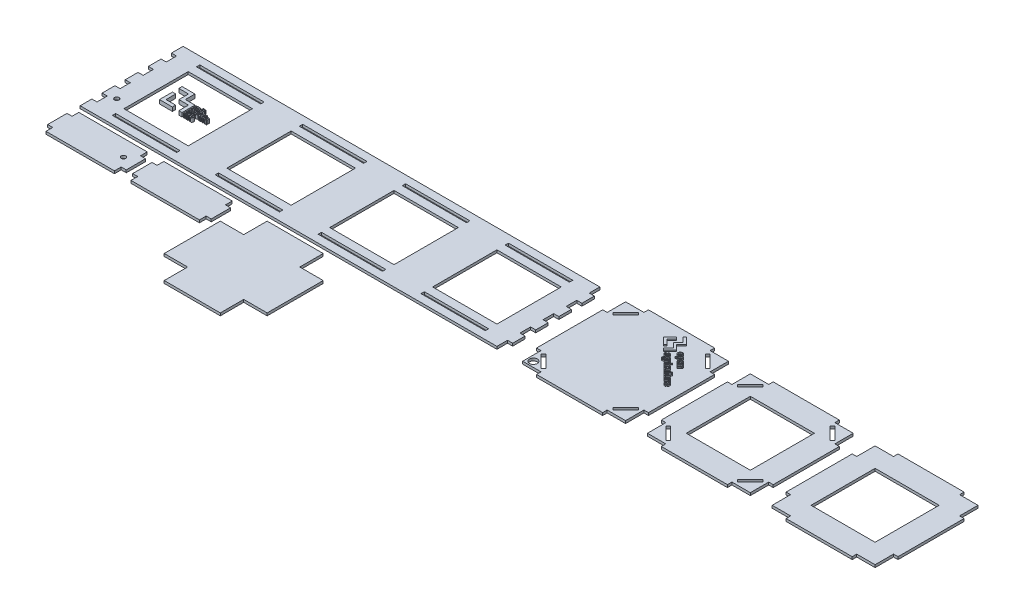
SolidWorks part; units mm, degrees
ref_plane "Front" through (0, 0, 0) normal (0, 0, 1) x (1, 0, 0)
ref_plane "Top" through (0, 0, 0) normal (0, 1, 0) x (1, 0, 0)
ref_plane "Right" through (0, 0, 0) normal (1, 0, 0) x (0, 0, -1)
sketch "Sketch1" plane through (0, 0, 0) normal (0, 1, 0) x (1, 0, 0)
  line L0 (0, 0) -> (152.4, 0) construction
  line L2 (-50.8, 50.8) -> (-50.8, -50.8) construction
  line L4 (50.8, 50.8) -> (50.8, -50.8) construction
  line L5 (-50.8, 50.8) -> (50.8, -50.8) construction
  line L6 (-50.8, -50.8) -> (50.8, 50.8) construction
  line L11 (50.8, 50.8) -> (152.4, 50.8)
  line L12 (50.8, 50.8) -> (50.8, -50.8) construction
  line L13 (50.8, -50.8) -> (152.4, -50.8)
  line L14 (152.4, 50.8) -> (152.4, -50.8) construction
  line L19 (-50.8, -50.8) -> (-152.4, -50.8)
  line L20 (-50.8, -50.8) -> (-50.8, 50.8) construction
  line L21 (-50.8, 50.8) -> (-152.4, 50.8)
  line L28 (50.8, -50.8) -> (-50.8, -50.8)
  line L34 (50.8, 50.8) -> (-50.8, 50.8)
  line L35 (-152.4, 50.8) -> (-152.4, -50.8) construction
  line L43 (-152.4, 50.8) -> (-254, 50.8)
  line L44 (-254, 50.8) -> (-254, -50.8) construction
  line L45 (-254, -50.8) -> (-152.4, -50.8)
  line L46 (152.4, 50.8) -> (152.4, 40.3352)
  line L47 (152.4, 40.3352) -> (157.48, 40.3352)
  line L48 (157.48, 40.3352) -> (157.48, 28.0162)
  line L49 (157.48, 28.0162) -> (152.4, 28.0162)
  line L50 (152.4, 28.0162) -> (152.4, 17.5514)
  line L51 (152.4, 17.5514) -> (157.48, 17.5514)
  line L63 (157.48, 17.5514) -> (157.48, 5.2324)
  line L64 (157.48, 5.2324) -> (152.4, 5.2324)
  line L65 (152.4, 5.2324) -> (152.4, -5.2324)
  line L66 (152.4, -5.2324) -> (157.48, -5.2324)
  line L67 (157.48, -5.2324) -> (157.48, -17.5514)
  line L68 (157.48, -17.5514) -> (152.4, -17.5514)
  line L69 (152.4, -17.5514) -> (152.4, -28.0162)
  line L70 (152.4, -28.0162) -> (157.48, -28.0162)
  line L71 (157.48, -28.0162) -> (157.48, -40.3352)
  line L72 (157.48, -40.3352) -> (152.4, -40.3352)
  line L73 (152.4, -40.3352) -> (152.4, -50.8)
  line L74 (-254, 50.8) -> (-259.08, 50.8)
  line L76 (-259.08, 39.2557) -> (-254, 39.2557)
  line L78 (-254, 29.0957) -> (-259.08, 29.0957)
  line L80 (-259.08, 16.4719) -> (-254, 16.4719)
  line L82 (-254, 6.3119) -> (-259.08, 6.3119)
  line L84 (-259.08, -6.3119) -> (-254, -6.3119)
  line L86 (-254, -16.4719) -> (-259.08, -16.4719)
  line L88 (-259.08, -29.0957) -> (-254, -29.0957)
  line L90 (-254, -39.2557) -> (-259.08, -39.2557)
  line L92 (-259.08, -50.8) -> (-254, -50.8)
  line L93 (157.48, 11.3919) -> (-254, 11.3919) construction
  line L94 (-254, 34.1757) -> (157.48, 34.1757) construction
  line L95 (-259.08, 50.8) -> (-259.08, 39.2557)
  line L96 (-259.08, 29.0957) -> (-259.08, 16.4719)
  line L97 (-254, 39.2557) -> (-254, 29.0957)
  line L98 (-254, 16.4719) -> (-254, 6.3119)
  line L99 (-254, -6.3119) -> (-254, -16.4719)
  line L100 (-254, -29.0957) -> (-254, -39.2557)
  line L101 (-254, -34.1757) -> (157.48, -34.1757) construction
  line L102 (-254, -11.3919) -> (157.48, -11.3919) construction
  line L103 (-259.08, 6.3119) -> (-259.08, -6.3119)
  line L104 (-259.08, -16.4719) -> (-259.08, -29.0957)
  line L105 (-259.08, -39.2557) -> (-259.08, -50.8)
  point P0 (0, 0)
  dimension "D1" = 101.6
  dimension "D2" = 101.6
  dimension "D3" = 5.08
  dimension "D4" = 12.319
  dimension "D5" = 10.16
extrude "Boss-Extrude1" add sketch "Sketch1" along normal blind 2.54
sketch "Sketch4" plane through (0, 2.54, 0) normal (0, 1, 0) x (1, 0, 0)
  line L0 (-152.4, 50.8) -> (-152.4, -50.8) construction
  line L1 (-152.4, 50.8) -> (-152.4, -50.8)
  line L2 (-50.8, 50.8) -> (-50.8, -50.8) construction
  line L3 (-50.8, 50.8) -> (-50.8, -50.8)
  line L4 (50.8, 50.8) -> (50.8, -50.8) construction
  line L5 (50.8, 50.8) -> (50.8, -50.8)
sketch "Sketch5" plane through (0, 2.54, 0) normal (0, 1, 0) x (1, 0, 0)
  line L0 (-254, -6.3119) -> (-254, 6.3119) construction
  line L1 (-152.4, 0) -> (-254, 0) construction
  line L2 (-152.4, 50.8) -> (-152.4, -50.8) construction
  line L3 (-152.4, 0) -> (-50.8, 0) construction
  line L4 (-50.8, 50.8) -> (-50.8, -50.8) construction
  line L5 (-50.8, 0) -> (50.8, 0) construction
  line L6 (50.8, 50.8) -> (50.8, -50.8) construction
  line L7 (50.8, 0) -> (152.4, 0) construction
  line L8 (152.4, -5.2324) -> (152.4, 5.2324) construction
  line L9 (-203.2, 0) -> (-203.2, -50.8) construction
  line L10 (-259.08, -50.8) -> (152.4, -50.8) construction
  line L11 (-101.6, 0) -> (-101.6, -50.8) construction
  line L12 (0, 0) -> (0, -50.8) construction
  line L13 (101.6, 0) -> (101.6, -50.8) construction
  line L14 (-171.45, -43.18) -> (-171.45, -50.8) construction
  line L15 (-234.95, -39.878) -> (-171.45, -39.878)
  line L16 (-234.95, -39.878) -> (-234.95, -43.18)
  line L17 (-234.95, -43.18) -> (-171.45, -43.18)
  line L18 (-171.45, -39.878) -> (-171.45, -43.18)
  line L19 (-234.95, -39.878) -> (-171.45, -43.18) construction
  line L20 (-234.95, -43.18) -> (-171.45, -39.878) construction
  line L21 (-133.35, -39.878) -> (-69.85, -39.878)
  line L22 (-133.35, -39.878) -> (-133.35, -43.18)
  line L23 (-133.35, -43.18) -> (-69.85, -43.18)
  line L24 (-69.85, -39.878) -> (-69.85, -43.18)
  line L25 (-133.35, -39.878) -> (-69.85, -43.18) construction
  line L26 (-133.35, -43.18) -> (-69.85, -39.878) construction
  line L27 (-31.75, -43.18) -> (31.75, -43.18)
  line L28 (-31.75, -43.18) -> (-31.75, -39.878)
  line L29 (-31.75, -39.878) -> (31.75, -39.878)
  line L30 (31.75, -43.18) -> (31.75, -39.878)
  line L31 (-31.75, -43.18) -> (31.75, -39.878) construction
  line L32 (-31.75, -39.878) -> (31.75, -43.18) construction
  line L33 (69.85, -43.18) -> (133.35, -43.18)
  line L34 (69.85, -43.18) -> (69.85, -39.878)
  line L35 (69.85, -39.878) -> (133.35, -39.878)
  line L36 (133.35, -43.18) -> (133.35, -39.878)
  line L37 (69.85, -43.18) -> (133.35, -39.878) construction
  line L38 (69.85, -39.878) -> (133.35, -43.18) construction
  line L39 (69.85, 39.878) -> (133.35, 43.18) construction
  line L40 (69.85, 43.18) -> (133.35, 39.878) construction
  line L41 (-31.75, 39.878) -> (31.75, 43.18) construction
  line L42 (-31.75, 43.18) -> (31.75, 39.878) construction
  line L43 (-133.35, 43.18) -> (-69.85, 39.878) construction
  line L44 (-133.35, 39.878) -> (-69.85, 43.18) construction
  line L45 (-234.95, 43.18) -> (-171.45, 39.878) construction
  line L46 (-234.95, 39.878) -> (-171.45, 43.18) construction
  line L47 (-171.45, 43.18) -> (-171.45, 50.8) construction
  line L48 (133.35, 43.18) -> (133.35, 39.878)
  line L49 (69.85, 39.878) -> (133.35, 39.878)
  line L50 (69.85, 43.18) -> (69.85, 39.878)
  line L51 (69.85, 43.18) -> (133.35, 43.18)
  line L52 (31.75, 43.18) -> (31.75, 39.878)
  line L53 (-31.75, 39.878) -> (31.75, 39.878)
  line L54 (-31.75, 43.18) -> (-31.75, 39.878)
  line L55 (-31.75, 43.18) -> (31.75, 43.18)
  line L56 (-69.85, 39.878) -> (-69.85, 43.18)
  line L57 (-133.35, 43.18) -> (-69.85, 43.18)
  line L58 (-133.35, 39.878) -> (-133.35, 43.18)
  line L59 (-133.35, 39.878) -> (-69.85, 39.878)
  line L60 (-171.45, 39.878) -> (-171.45, 43.18)
  line L61 (-234.95, 43.18) -> (-171.45, 43.18)
  line L62 (-234.95, 39.878) -> (-234.95, 43.18)
  line L63 (-234.95, 39.878) -> (-171.45, 39.878)
  line L65 (-234.95, 31.75) -> (-171.45, 31.75)
  line L66 (-234.95, 31.75) -> (-234.95, -31.75)
  line L67 (-234.95, -31.75) -> (-171.45, -31.75)
  line L68 (-171.45, 31.75) -> (-171.45, -31.75)
  line L69 (-234.95, 31.75) -> (-171.45, -31.75) construction
  line L70 (-234.95, -31.75) -> (-171.45, 31.75) construction
  line L71 (-133.35, 31.75) -> (-69.85, 31.75)
  line L72 (-133.35, 31.75) -> (-133.35, -31.75)
  line L73 (-133.35, -31.75) -> (-69.85, -31.75)
  line L74 (-69.85, 31.75) -> (-69.85, -31.75)
  line L75 (-133.35, 31.75) -> (-69.85, -31.75) construction
  line L76 (-133.35, -31.75) -> (-69.85, 31.75) construction
  line L77 (-31.75, 31.75) -> (31.75, 31.75)
  line L78 (-31.75, 31.75) -> (-31.75, -31.75)
  line L79 (-31.75, -31.75) -> (31.75, -31.75)
  line L80 (31.75, 31.75) -> (31.75, -31.75)
  line L81 (-31.75, 31.75) -> (31.75, -31.75) construction
  line L82 (-31.75, -31.75) -> (31.75, 31.75) construction
  line L83 (69.85, 31.75) -> (133.35, 31.75)
  line L84 (69.85, 31.75) -> (69.85, -31.75)
  line L85 (69.85, -31.75) -> (133.35, -31.75)
  line L86 (133.35, 31.75) -> (133.35, -31.75)
  line L87 (69.85, 31.75) -> (133.35, -31.75) construction
  line L88 (69.85, -31.75) -> (133.35, 31.75) construction
  circle A0 centre (-246.95, -26.75) radius 2.2225
  point P27 (-203.2, -41.529)
  point P32 (-101.6, -41.529)
  point P37 (0, -41.529)
  point P42 (101.6, -41.529)
  point P66 (101.6, 41.529)
  point P67 (0, 41.529)
  point P68 (-101.6, 41.529)
  point P69 (-203.2, 41.529)
  dimension "D5" = 4.445
  dimension "D7" = 5
  dimension "D1" = 7.62
  dimension "D2" = 3.302
  dimension "D3" = 63.5
  dimension "D4" = 63.5
  dimension "D6" = 12
extrude "Cut-Extrude2" cut sketch "Sketch5" against normal through all
sketch "Sketch6" plane through (0, 0, 0) normal (0, 1, 0) x (1, 0, 0)
  line L0 (0, 0) -> (228.6, 0) construction
  line L1 (228.6, 0) -> (228.6, 53.0225) construction
  line L2 (177.8, 50.8) -> (279.4, 50.8) construction
  line L3 (177.8, 50.8) -> (177.8, -50.8) construction
  line L4 (177.8, -50.8) -> (279.4, -50.8) construction
  line L5 (279.4, 50.8) -> (279.4, -50.8) construction
  line L6 (177.8, 50.8) -> (279.4, -50.8) construction
  line L7 (177.8, -50.8) -> (279.4, 50.8) construction
  line L8 (228.6, 0) -> (281.6225, 0) construction
  line L9 (228.6, 0) -> (228.6, -53.0225) construction
  line L10 (177.8, 32.639) -> (177.8, 50.8)
  line L11 (195.961, 55.245) -> (261.239, 55.245)
  line L12 (195.961, 55.245) -> (195.961, 50.8)
  line L13 (195.961, 50.8) -> (261.239, 50.8) construction
  line L14 (261.239, 55.245) -> (261.239, 50.8)
  line L15 (195.961, 55.245) -> (261.239, 50.8) construction
  line L16 (195.961, 50.8) -> (261.239, 55.245) construction
  line L17 (283.845, -32.639) -> (279.4, -32.639)
  line L18 (283.845, -32.639) -> (283.845, 32.639)
  line L19 (283.845, 32.639) -> (279.4, 32.639)
  line L20 (279.4, -32.639) -> (279.4, 32.639) construction
  line L21 (283.845, -32.639) -> (279.4, 32.639) construction
  line L22 (283.845, 32.639) -> (279.4, -32.639) construction
  line L23 (195.961, -55.245) -> (261.239, -55.245)
  line L24 (195.961, -55.245) -> (195.961, -50.8)
  line L25 (195.961, -50.8) -> (261.239, -50.8) construction
  line L26 (261.239, -55.245) -> (261.239, -50.8)
  line L27 (195.961, -55.245) -> (261.239, -50.8) construction
  line L28 (195.961, -50.8) -> (261.239, -55.245) construction
  line L29 (173.355, 32.639) -> (177.8, 32.639)
  line L30 (173.355, 32.639) -> (173.355, -32.639)
  line L31 (173.355, -32.639) -> (177.8, -32.639)
  line L32 (177.8, 32.639) -> (177.8, -32.639) construction
  line L33 (173.355, 32.639) -> (177.8, -32.639) construction
  line L34 (173.355, -32.639) -> (177.8, 32.639) construction
  line L35 (177.8, 50.8) -> (195.961, 50.8)
  line L36 (261.239, 50.8) -> (279.4, 50.8)
  line L37 (279.4, 50.8) -> (279.4, 32.639)
  line L38 (279.4, -32.639) -> (279.4, -50.8)
  line L39 (279.4, -50.8) -> (261.239, -50.8)
  line L40 (195.961, -50.8) -> (177.8, -50.8)
  line L41 (177.8, -50.8) -> (177.8, -32.639)
  line L42 (296.545, 32.639) -> (296.545, -32.639)
  line L43 (296.545, 32.639) -> (300.99, 32.639)
  line L44 (300.99, 32.639) -> (300.99, 50.8)
  line L45 (300.99, 50.8) -> (319.151, 50.8)
  line L46 (319.151, 55.245) -> (319.151, 50.8)
  line L47 (319.151, 55.245) -> (384.429, 55.245)
  line L48 (384.429, 55.245) -> (384.429, 50.8)
  line L49 (384.429, 50.8) -> (402.59, 50.8)
  line L50 (402.59, 50.8) -> (402.59, 32.639)
  line L51 (407.035, 32.639) -> (402.59, 32.639)
  line L52 (407.035, -32.639) -> (407.035, 32.639)
  line L53 (407.035, -32.639) -> (402.59, -32.639)
  line L54 (402.59, -32.639) -> (402.59, -50.8)
  line L55 (402.59, -50.8) -> (384.429, -50.8)
  line L56 (384.429, -55.245) -> (384.429, -50.8)
  line L57 (319.151, -55.245) -> (384.429, -55.245)
  line L58 (319.151, -55.245) -> (319.151, -50.8)
  line L59 (319.151, -50.8) -> (300.99, -50.8)
  line L60 (300.99, -50.8) -> (300.99, -32.639)
  line L61 (296.545, -32.639) -> (300.99, -32.639)
  line L62 (300.99, 50.8) -> (402.59, -50.8) construction
  line L63 (419.735, 32.639) -> (419.735, -32.639)
  line L64 (419.735, 32.639) -> (424.18, 32.639)
  line L65 (424.18, 32.639) -> (424.18, 50.8)
  line L66 (424.18, 50.8) -> (442.341, 50.8)
  line L67 (442.341, 55.245) -> (442.341, 50.8)
  line L68 (442.341, 55.245) -> (507.619, 55.245)
  line L69 (507.619, 55.245) -> (507.619, 50.8)
  line L70 (507.619, 50.8) -> (525.78, 50.8)
  line L71 (525.78, 50.8) -> (525.78, 32.639)
  line L72 (530.225, 32.639) -> (525.78, 32.639)
  line L73 (530.225, -32.639) -> (530.225, 32.639)
  line L74 (530.225, -32.639) -> (525.78, -32.639)
  line L75 (525.78, -32.639) -> (525.78, -50.8)
  line L76 (525.78, -50.8) -> (507.619, -50.8)
  line L77 (507.619, -55.245) -> (507.619, -50.8)
  line L78 (442.341, -55.245) -> (507.619, -55.245)
  line L79 (442.341, -55.245) -> (442.341, -50.8)
  line L80 (442.341, -50.8) -> (424.18, -50.8)
  line L81 (424.18, -50.8) -> (424.18, -32.639)
  line L82 (419.735, -32.639) -> (424.18, -32.639)
  line L83 (424.18, 50.8) -> (525.78, -50.8) construction
  line L84 (320.167, 31.623) -> (383.413, 31.623)
  line L85 (320.167, 31.623) -> (320.167, -31.623)
  line L86 (320.167, -31.623) -> (383.413, -31.623)
  line L87 (383.413, 31.623) -> (383.413, -31.623)
  line L88 (320.167, 31.623) -> (383.413, -31.623) construction
  line L89 (320.167, -31.623) -> (383.413, 31.623) construction
  line L91 (506.603, 31.623) -> (443.357, 31.623)
  line L92 (506.603, 31.623) -> (506.603, -31.623)
  line L93 (506.603, -31.623) -> (443.357, -31.623)
  line L94 (443.357, 31.623) -> (443.357, -31.623)
  line L95 (506.603, 31.623) -> (443.357, -31.623) construction
  line L96 (506.603, -31.623) -> (443.357, 31.623) construction
  point P22 (175.5775, 0)
  point P67 (351.79, 0)
  point P72 (474.98, 0)
  dimension "D1" = 101.6
  dimension "D2" = 101.6
  dimension "D3" = 4.445
  dimension "D4" = 65.278
  dimension "D5" = 228.6
  dimension "D7" = 12.7
  dimension "D8" = 63.246
  dimension "D6" = 3
extrude "Boss-Extrude2" add sketch "Sketch6" along normal blind 2.54 separate body
sketch "Sketch7" plane through (0, 0, 0) normal (0, 1, 0) x (1, 0, 0)
  line L0 (-234.95, 39.878) -> (-234.95, -27.686) construction
  line L1 (-254.08, -57.15) -> (-186.516, -57.15)
  line L2 (-254.08, -57.15) -> (-254.08, -63.8175)
  line L3 (-254.08, -89.535) -> (-186.516, -89.535)
  line L4 (-186.516, -57.15) -> (-186.516, -63.8175)
  line L5 (-254.08, -57.15) -> (-186.516, -89.535) construction
  line L6 (-254.08, -89.535) -> (-186.516, -57.15) construction
  line L7 (-234.95, 31.75) -> (-234.95, -31.75) construction
  line L8 (-234.95, -27.686) -> (-234.95, -31.75) construction
  line L9 (177.8, -32.639) -> (177.8, -50.8) construction
  line L10 (177.8, -50.8) -> (195.961, -50.8) construction
  line L12 (-254.08, -63.8175) -> (-259.08, -63.8175)
  line L13 (182.9292, -33.0985) -> (195.5015, -45.6708) construction
  line L14 (182.9292, -33.0985) -> (180.5943, -35.4333) construction
  line L15 (180.5943, -35.4333) -> (193.1667, -48.0057) construction
  line L16 (195.5015, -45.6708) -> (193.1667, -48.0057) construction
  line L17 (182.9292, -33.0985) -> (193.1667, -48.0057) construction
  line L18 (180.5943, -35.4333) -> (195.5015, -45.6708) construction
  line L19 (-259.08, -63.8175) -> (-259.08, -82.8675)
  line L20 (-259.08, -82.8675) -> (-254.08, -82.8675)
  line L21 (177.8, -32.639) -> (195.961, -50.8) construction
  line L22 (188.0479, -40.5521) -> (186.8805, -41.7195) construction
  line L23 (-254.08, -82.8675) -> (-254.08, -89.535)
  line L24 (-186.516, -63.8175) -> (-181.516, -63.8175)
  line L25 (-181.516, -63.8175) -> (-181.516, -82.8675)
  line L26 (-181.516, -82.8675) -> (-186.516, -82.8675)
  line L27 (-186.516, -82.8675) -> (-186.516, -89.535)
  line L28 (-259.08, -50.8) -> (152.4, -50.8) construction
  line L29 (-259.08, -39.2557) -> (-259.08, -50.8) construction
  line L30 (-170.166, -57.15) -> (-102.602, -57.15)
  line L31 (-170.166, -57.15) -> (-170.166, -63.8175)
  line L32 (-170.166, -89.535) -> (-102.602, -89.535)
  line L33 (-102.602, -57.15) -> (-102.602, -63.8175)
  line L34 (-170.166, -63.8175) -> (-175.166, -63.8175)
  line L35 (-175.166, -63.8175) -> (-175.166, -82.8675)
  line L36 (-175.166, -82.8675) -> (-170.166, -82.8675)
  line L37 (-170.166, -82.8675) -> (-170.166, -89.535)
  line L38 (-102.602, -63.8175) -> (-97.602, -63.8175)
  line L39 (-97.602, -63.8175) -> (-97.602, -82.8675)
  line L40 (-97.602, -82.8675) -> (-102.602, -82.8675)
  line L41 (-102.602, -82.8675) -> (-102.602, -89.535)
  line L42 (-170.166, -57.15) -> (-102.602, -89.535) construction
  line L43 (-170.166, -89.535) -> (-102.602, -57.15) construction
  point P0 (-220.298, -73.3425)
  point P14 (188.0479, -40.5521)
  point P38 (-136.384, -73.3425)
  dimension "D1" = 32.385
  dimension "D2" = 4.064
  dimension "D3" = 3.302
  dimension "D4" = 19.05
  dimension "D5" = 17.78
  dimension "D6" = 5
  dimension "D7" = 6.35
  dimension "D9" = 6.35
  dimension "D8" = 2
extrude "Boss-Extrude3" add sketch "Sketch7" along normal blind 2.54 separate body
sketch "Sketch8" plane through (0, 2.54, 0) normal (0, 1, 0) x (1, 0, 0)
  line L0 (180.5943, -35.4333) -> (193.1667, -48.0057) construction
  line L1 (195.5015, -45.6708) -> (193.1667, -48.0057) construction
  line L2 (182.9292, -33.0985) -> (195.5015, -45.6708) construction
  line L3 (182.9292, -33.0985) -> (180.5943, -35.4333) construction
  line L4 (180.5943, -35.4333) -> (193.1667, -48.0057)
  line L5 (195.5015, -45.6708) -> (193.1667, -48.0057)
  line L6 (182.9292, -33.0985) -> (195.5015, -45.6708)
  line L7 (182.9292, -33.0985) -> (180.5943, -35.4333)
  line L8 (177.8, 50.8) -> (279.4, -50.8) construction
  line L9 (195.5015, 45.6708) -> (182.9292, 33.0985)
  line L10 (195.5015, 45.6708) -> (193.1667, 48.0057)
  line L11 (193.1667, 48.0057) -> (180.5943, 35.4333)
  line L12 (182.9292, 33.0985) -> (180.5943, 35.4333)
  line L13 (274.2708, 33.0985) -> (261.6985, 45.6708)
  line L14 (274.2708, 33.0985) -> (276.6057, 35.4333)
  line L15 (276.6057, 35.4333) -> (264.0333, 48.0057)
  line L16 (261.6985, 45.6708) -> (264.0333, 48.0057)
  line L17 (261.6985, -45.6708) -> (274.2708, -33.0985)
  line L18 (261.6985, -45.6708) -> (264.0333, -48.0057)
  line L19 (264.0333, -48.0057) -> (276.6057, -35.4333)
  line L20 (274.2708, -33.0985) -> (276.6057, -35.4333)
  line L21 (300.99, -32.639) -> (319.151, -50.8) construction
  line L22 (303.7843, -35.4333) -> (306.1192, -33.0985)
  line L23 (306.1192, -33.0985) -> (318.6915, -45.6708)
  line L24 (318.6915, -45.6708) -> (316.3567, -48.0057)
  line L25 (310.0705, -41.7195) -> (312.4054, -39.3846) construction
  line L26 (303.7843, -35.4333) -> (316.3567, -48.0057)
  line L27 (300.99, 50.8) -> (402.59, -50.8) construction
  line L28 (306.1192, 33.0985) -> (303.7843, 35.4333)
  line L29 (316.3567, 48.0057) -> (303.7843, 35.4333)
  line L30 (316.3567, 48.0057) -> (318.6915, 45.6708)
  line L31 (318.6915, 45.6708) -> (306.1192, 33.0985)
  line L32 (384.8885, 45.6708) -> (387.2233, 48.0057)
  line L33 (399.7957, 35.4333) -> (387.2233, 48.0057)
  line L34 (399.7957, 35.4333) -> (397.4608, 33.0985)
  line L35 (397.4608, 33.0985) -> (384.8885, 45.6708)
  line L36 (397.4608, -33.0985) -> (399.7957, -35.4333)
  line L37 (387.2233, -48.0057) -> (399.7957, -35.4333)
  line L38 (387.2233, -48.0057) -> (384.8885, -45.6708)
  line L39 (384.8885, -45.6708) -> (397.4608, -33.0985)
  circle A0 centre (228.6, 0) radius 20.7898 construction
  circle A1 centre (228.6, 0) radius 20.7898 construction
  circle A2 centre (228.6, 0) radius 20.7898 construction
  circle A3 centre (228.6, 0) radius 20.7898 construction
  circle A4 centre (351.79, 0) radius 44.7217 construction
  point P28 (228.6, 0)
  point P58 (351.79, 0)
  dimension "D1" = 4
  dimension "D2" = 4
extrude "Cut-Extrude3" cut sketch "Sketch8" against normal through all
sketch "Sketch10" plane through (0, 2.54, 0) normal (0, 1, 0) x (1, 0, 0)
  line L0 (-171.45, 31.75) -> (-234.95, 31.75) construction
  line L1 (-69.85, 31.75) -> (-133.35, 31.75) construction
  line L2 (31.75, 31.75) -> (-31.75, 31.75) construction
  line L3 (133.35, 31.75) -> (69.85, 31.75) construction
  line L4 (-196.85, 31.75) -> (-209.55, 31.75)
  line L5 (-95.25, 31.75) -> (-107.95, 31.75)
  line L6 (6.35, 31.75) -> (-6.35, 31.75)
  line L7 (107.95, 31.75) -> (95.25, 31.75)
  line L8 (-234.95, -27.686) -> (-171.45, -27.686)
  line L9 (-203.2, -27.686) -> (-203.2, -31.75) construction
  line L14 (-234.95, 31.75) -> (-234.95, -31.75) construction
  line L15 (-171.45, -31.75) -> (-171.45, 31.75) construction
  line L16 (-234.95, -31.75) -> (-171.45, -31.75) construction
  line L17 (-133.35, -27.686) -> (-69.85, -27.686)
  line L18 (-133.35, 31.75) -> (-133.35, -31.75) construction
  line L19 (-69.85, -31.75) -> (-69.85, 31.75) construction
  line L20 (-31.75, -27.686) -> (31.75, -27.686)
  line L21 (-31.75, 31.75) -> (-31.75, -31.75) construction
  line L22 (31.75, -31.75) -> (31.75, 31.75) construction
  line L23 (69.85, -27.686) -> (133.35, -27.686)
  line L24 (69.85, 31.75) -> (69.85, -31.75) construction
  line L25 (133.35, -31.75) -> (133.35, 31.75) construction
  line L27 (-234.95, 31.75) -> (-234.95, -27.686) construction
  arc A0 (-209.55, 31.75) -> (-196.85, 31.75) centre (-203.2, 31.75) ccw
  arc A1 (-107.95, 31.75) -> (-95.25, 31.75) centre (-101.6, 31.75) ccw
  arc A2 (-6.35, 31.75) -> (6.35, 31.75) centre (0, 31.75) ccw
  arc A3 (95.25, 31.75) -> (107.95, 31.75) centre (101.6, 31.75) ccw
  point P49 (-234.95, -7.599)
  point P51 (-203.2, -28.721)
  dimension "D1" = 12.7
  dimension "D2" = 4.064
sketch "Sketch11" plane through (0, 0, 0) normal (0, 1, 0) x (1, 0, 0)
  line L0 (-133.35, -31.75) -> (-133.35, -39.878) construction
  line L5 (-68.138, -80.264) -> (-12.766, -80.264) construction
  line L6 (-68.138, -80.264) -> (-68.138, -135.636) construction
  line L7 (-68.138, -135.636) -> (-12.766, -135.636) construction
  line L8 (-12.766, -80.264) -> (-12.766, -135.636) construction
  line L9 (-68.138, -80.264) -> (-12.766, -135.636) construction
  line L10 (-68.138, -135.636) -> (-12.766, -80.264) construction
  line L11 (-68.138, -80.264) -> (-91.252, -80.264)
  line L12 (-91.252, -80.264) -> (-91.252, -135.636)
  line L13 (-91.252, -135.636) -> (-68.138, -135.636)
  line L14 (-68.138, -80.264) -> (-68.138, -57.15)
  line L15 (-68.138, -57.15) -> (-12.766, -57.15)
  line L16 (-12.766, -57.15) -> (-12.766, -80.264)
  line L17 (-12.766, -80.264) -> (10.348, -80.264)
  line L18 (10.348, -80.264) -> (10.348, -135.636)
  line L19 (10.348, -135.636) -> (-12.766, -135.636)
  line L20 (-12.766, -135.636) -> (-12.766, -158.75)
  line L21 (-12.766, -158.75) -> (-68.138, -158.75)
  line L22 (-68.138, -158.75) -> (-68.138, -135.636)
  line L23 (-259.08, -50.8) -> (152.4, -50.8) construction
  line L24 (-97.602, -82.8675) -> (-97.602, -63.8175) construction
  line L27 (133.35, -27.686) -> (133.35, -50.8) construction
  point P0 (-40.452, -107.95)
  point P17 (-12.766, -155.7828)
  point P26 (18.3678, -143.51)
  point P27 (10.4899, -166.624)
  point P28 (9.8334, -189.4024)
  point P29 (42.6578, -158.5475)
  point P30 (14.9531, -143.51)
  point P31 (-0.8391, -182.9548)
  dimension "D1" = 55.372
  dimension "D4" = 6.35
  dimension "D5" = 6.35
extrude "Boss-Extrude5" add sketch "Sketch11" along normal blind 2.54 separate body
sketch "Sketch12" plane through (0, 2.54, 0) normal (0, 1, 0) x (1, 0, 0)
  line L0 (-68.138, -80.264) -> (-12.766, -80.264)
  line L1 (-12.766, -80.264) -> (-12.766, -135.636)
  line L2 (-12.766, -135.636) -> (-68.138, -135.636)
  line L3 (-68.138, -80.264) -> (-68.138, -135.636)
sketch "Sketch13" plane through (0, 0, 0) normal (0, 1, 0) x (1, 0, 0)
  line L16 (-223.9443, 14.6616) -> (-211.1797, 14.6616)
  line L17 (-211.1797, 14.6616) -> (-211.1797, 5.1786)
  line L18 (-211.1797, 5.1786) -> (-201.7193, 5.1786)
  line L19 (239.1402, 49.5353) -> (245.5874, 43.0882)
  line L20 (245.5874, 43.0882) -> (240.7977, 38.2986)
  line L21 (240.7977, 38.2986) -> (245.5759, 33.5204)
  line L22 (245.5759, 33.5204) -> (239.1174, 27.0618)
  line L24 (237.5056, 28.6736) -> (242.3295, 33.4975)
  line L25 (242.3295, 33.4975) -> (237.5627, 38.2643)
  line L26 (237.5627, 38.2643) -> (242.3752, 43.0768)
  line L27 (242.3752, 43.0768) -> (237.5284, 47.9235)
  line L28 (237.5284, 47.9235) -> (239.1402, 49.5353)
  line L29 (234.3506, 44.7457) -> (235.9738, 43.1225)
  line L30 (235.9738, 43.1225) -> (231.1385, 38.2871)
  line L31 (231.1385, 38.2871) -> (235.9624, 33.4632)
  line L32 (235.9624, 33.4632) -> (234.3392, 31.84)
  line L33 (234.3392, 31.84) -> (227.892, 38.2871)
  line L34 (227.892, 38.2871) -> (234.3506, 44.7457)
  line L36 (239.5771, 26.9975) -> (266.5291, 0.0455) construction
  line L37 (247.4273, 32.1428) -> (285.1667, -5.5965) construction
  line L38 (237.5056, 28.6736) -> (239.1174, 27.0618)
  line L41 (-201.7193, 5.1786) -> (-201.7193, -7.6086)
  line L43 (-204.9105, -7.6086) -> (-204.9105, 1.9422)
  line L44 (-204.9105, 1.9422) -> (-214.3482, 1.9422)
  line L45 (-214.3482, 1.9422) -> (-214.3482, 11.4705)
  line L46 (-214.3482, 11.4705) -> (-223.9443, 11.4705)
  line L47 (-223.9443, 11.4705) -> (-223.9443, 14.6616)
  line L48 (-223.9443, 5.1786) -> (-220.7305, 5.1786)
  line L49 (-220.7305, 5.1786) -> (-220.7305, -4.3949)
  line L50 (-220.7305, -4.3949) -> (-211.1797, -4.3949)
  line L51 (-211.1797, -4.3949) -> (-211.1797, -7.6086)
  line L52 (-211.1797, -7.6086) -> (-223.9443, -7.6086)
  line L53 (-223.9443, -7.6086) -> (-223.9443, 5.1786)
  line L54 (-200.854, -7.608) -> (-149.188, -7.608) construction
  line L55 (-234.95, 31.75) -> (-171.45, -27.686) construction
  line L56 (-204.9105, -7.6086) -> (-201.7193, -7.6086)
  line L57 (-200.854, -7.608) -> (-200.854, 5.1786) construction
  line L58 (-200.854, 5.1786) -> (-201.7193, 5.1786) construction
  line L59 (-200.854, 1.9422) -> (-182.9615, 1.9422) construction
  line L60 (-200.854, -2.3557) -> (-181.4784, -2.3557) construction
  line L61 (-234.95, 31.75) -> (-234.95, -31.75) construction
  line L62 (-196.85, 6.35) -> (-209.55, 6.35) construction
  line L63 (-196.85, 6.35) -> (-196.85, -2.286) construction
  line L64 (-196.85, -2.286) -> (-209.55, -2.286) construction
  line L65 (-209.55, 6.35) -> (-209.55, -2.286) construction
  line L66 (-196.85, 6.35) -> (-209.55, -2.286) construction
  line L67 (-196.85, -2.286) -> (-209.55, 6.35) construction
  line L68 (-171.45, 31.75) -> (-234.95, 31.75) construction
  line L69 (-234.95, -27.686) -> (-171.45, -27.686) construction
  line L70 (-171.45, -31.75) -> (-171.45, 31.75) construction
  text T0 "mit" font "Arial" height in points 18
  text T1 "media" font "Arial" height in points 18
  text T2 "lab" font "Arial" height in points 18
  text T3 "open" font "Arial" height in points 24
  text T4 " agriculture" font "Arial" height in points 24
  point P56 (-194.7375, 4.459)
  dimension "D1" = 25.4
  dimension "D4" = 25.4
  dimension "D5" = 25.4
  dimension "D6" = 25.4
sketch "Sketch14" plane through (0, 2.54, 0) normal (0, 1, 0) x (1, 0, 0)
  line L0 (-181.516, -73.3425) -> (-193.7385, -73.3425) construction
  line L1 (-181.516, -82.8675) -> (-181.516, -63.8175) construction
  circle A0 centre (-193.7385, -73.3425) radius 2.2225
  circle A1 centre (-246.95, -26.75) radius 2.2225 construction
  dimension "D1" = 10
extrude "Cut-Extrude4" cut sketch "Sketch14" against normal through all
extrude "Boss-Extrude7" add sketch "Sketch13" along normal blind 3.81 separate body
sketch "Sketch15" plane through (0, 2.54, 0) normal (0, 1, 0) x (1, 0, 0)
  line L0 (177.8, -50.8) -> (186.8805, -41.7195) construction
  line L1 (180.5943, -35.4333) -> (193.1667, -48.0057) construction
  line L2 (183.1192, -51.5768) -> (183.1192, -50.8) construction
  line L3 (177.8, -50.8) -> (195.961, -50.8) construction
  line L4 (186.8805, -41.7195) -> (187.4298, -41.1702) construction
  line L5 (177.8, 50.8) -> (279.4, -50.8) construction
  circle A0 centre (183.1192, -45.4808) radius 3.8725
  circle A1 centre (183.1192, -45.4808) radius 6.096 construction
  dimension "D1" = 7.745
  dimension "D2" = 12.192
extrude "Cut-Extrude5" cut sketch "Sketch15" against normal through all
sketch "Sketch16" plane through (0, 2.54, 0) normal (0, 1, 0) x (1, 0, 0)
  line L0 (320.167, 31.623) -> (320.167, -31.623) construction
  line L1 (323.342, -0.127) -> (481.6251, -0.127) construction
  line L2 (323.342, 18.923) -> (361.442, 18.923)
  line L3 (323.342, 18.923) -> (323.342, -19.177)
  line L4 (323.342, -19.177) -> (361.442, -19.177)
  line L6 (323.342, 18.923) -> (361.442, -19.177) construction
  line L7 (323.342, -19.177) -> (361.442, 18.923) construction
  line L8 (481.6251, -0.127) -> (342.392, -0.127) construction
  line L9 (361.442, 18.923) -> (361.442, 2.2474)
  line L10 (365.8568, 5.4246) -> (365.7722, 5.5711)
  line L11 (342.392, 18.923) -> (342.392, -19.177) construction
  line L12 (355.092, 4.953) -> (345.694, 4.953)
  line L13 (355.092, -5.207) -> (345.694, -5.207)
  line L14 (342.392, 4.953) -> (342.392, -5.207) construction
  line L15 (365.506, 4.953) -> (342.392, 4.953) construction
  line L16 (365.506, -5.207) -> (342.392, -5.207) construction
  line L17 (358.2953, 4.0858) -> (362.9562, 1.3627)
  line L18 (365.506, -0.127) -> (364.7832, -0.127) construction
  line L19 (365.506, -0.127) -> (342.392, -0.127) construction
  line L20 (380.7621, -0.127) -> (364.7832, -0.127) construction
  line L21 (355.092, 4.953) -> (355.092, -5.207) construction
  line L22 (361.442, -9.6369) -> (361.442, -19.177)
  line L23 (383.413, 31.623) -> (320.167, 31.623) construction
  line L24 (342.392, 8.255) -> (342.392, 8.763) construction
  line L25 (342.392, -8.509) -> (342.392, -9.017) construction
  line L26 (342.392, 8.255) -> (342.392, -8.509)
  arc A1 (365.8962, -1.7464) -> (369.1838, 3.4269) centre (369.062, -0.127) ccw
  arc A3 (369.3268, 11.5701) -> (365.7722, 5.5711) centre (369.2363, 7.5711) ccw
  arc A4 (365.8568, 5.4246) -> (369.1838, 3.4269) centre (369.3209, 7.4246) ccw
  arc A5 (358.2953, 4.0858) -> (355.092, 4.953) centre (355.092, -1.397) ccw
  arc A6 (360.0066, -7.5359) -> (355.092, -5.207) centre (355.092, -11.557) ccw
  arc A7 (365.8962, -1.7464) -> (362.9562, 1.3627) centre (359.1122, -5.2167) ccw
  arc A8 (345.694, -5.207) -> (342.392, -8.509) centre (345.694, -8.509) ccw
  arc A9 (342.392, 8.255) -> (345.694, 4.953) centre (345.694, 8.255) ccw
  arc A10 (360.0066, -7.5359) -> (369.3268, 11.5701) centre (369.062, -0.127) ccw
  point P4 (342.392, -0.127)
  point P28 (371.8905, 14.7821)
  point P49 (393.1829, -0.127)
  dimension "D7" = 4
  dimension "D8" = 6.35
  dimension "D9" = 6.35
  dimension "D10" = 7.62
  dimension "D12" = 7.112
  dimension "D17" = 3.302
  dimension "D1" = 38.1
  dimension "D2" = 38.1
  dimension "D3" = 12.7
  dimension "D4" = 5.08
  dimension "D6" = 30
  dimension "D11" = 26.67
  dimension "D13" = 3.175
  dimension "D14" = 12.7
  dimension "D15" = 3.81
  dimension "D16" = 3.81
  dimension "D5" = 5.08
sketch "Sketch17" plane through (0, 2.54, 0) normal (0, 1, 0) x (1, 0, 0)
  line L5 (323.342, 18.923) -> (361.442, 18.923) construction
  line L6 (323.342, 18.923) -> (361.442, 18.923)
  line L7 (361.442, 18.923) -> (361.442, 2.2474) construction
  line L8 (323.342, 18.923) -> (323.342, -19.177) construction
  line L9 (323.342, -19.177) -> (361.442, -19.177) construction
  line L14 (361.442, -9.6369) -> (361.442, -19.177) construction
  line L15 (361.442, 18.923) -> (361.442, 2.2474)
  line L16 (355.092, 4.953) -> (345.694, 4.953)
  line L17 (342.392, 8.255) -> (342.392, -8.509)
  line L18 (345.694, -5.207) -> (355.092, -5.207)
  line L19 (365.7722, 5.5711) -> (365.8568, 5.4246)
  line L20 (362.9562, 1.3627) -> (358.2953, 4.0858)
  line L21 (355.092, 4.953) -> (345.694, 4.953)
  line L23 (345.694, -5.207) -> (355.092, -5.207)
  line L24 (365.7722, 5.5711) -> (365.8568, 5.4246)
  line L25 (362.9562, 1.3627) -> (358.2953, 4.0858)
  line L26 (323.342, 18.923) -> (361.442, 18.923)
  line L27 (323.342, 18.923) -> (323.342, -19.177)
  line L28 (323.342, -19.177) -> (361.442, -19.177)
  line L29 (361.442, -9.0055) -> (361.442, -19.177)
  arc A18 (342.392, 8.255) -> (345.694, 4.953) centre (345.694, 8.255) ccw
  arc A19 (345.694, -5.207) -> (342.392, -8.509) centre (345.694, -8.509) ccw
  arc A20 (360.0066, -7.5359) -> (355.092, -5.207) centre (355.092, -11.557) ccw
  arc A21 (360.0066, -7.5359) -> (369.3268, 11.5701) centre (369.062, -0.127) ccw
  arc A22 (369.3268, 11.5701) -> (365.7722, 5.5711) centre (369.2363, 7.5711) ccw
  arc A23 (365.8568, 5.4246) -> (369.1838, 3.4269) centre (369.3209, 7.4246) ccw
  arc A24 (365.8962, -1.7464) -> (369.1838, 3.4269) centre (369.062, -0.127) ccw
  arc A25 (365.8962, -1.7464) -> (362.9562, 1.3627) centre (359.1122, -5.2167) ccw
  arc A26 (358.2953, 4.0858) -> (355.092, 4.953) centre (355.092, -1.397) ccw
  arc A27 (342.392, 8.255) -> (345.694, 4.953) centre (345.694, 8.255) ccw
  arc A28 (345.694, -5.207) -> (342.392, -8.509) centre (345.694, -8.509) ccw
  arc A29 (360.0066, -7.5359) -> (355.092, -5.207) centre (355.092, -11.557) ccw
  arc A30 (360.0066, -7.5359) -> (369.3268, 11.5701) centre (369.062, -0.127) ccw
  arc A31 (369.3268, 11.5701) -> (365.7722, 5.5711) centre (369.2363, 7.5711) ccw
  arc A32 (365.8568, 5.4246) -> (369.1838, 3.4269) centre (369.3209, 7.4246) ccw
  arc A33 (365.8962, -1.7464) -> (369.1838, 3.4269) centre (369.062, -0.127) ccw
  arc A34 (365.8962, -1.7464) -> (362.9562, 1.3627) centre (359.1122, -5.2167) ccw
  arc A35 (358.2953, 4.0858) -> (355.092, 4.953) centre (355.092, -1.397) ccw
  dimension "D1" = 0
